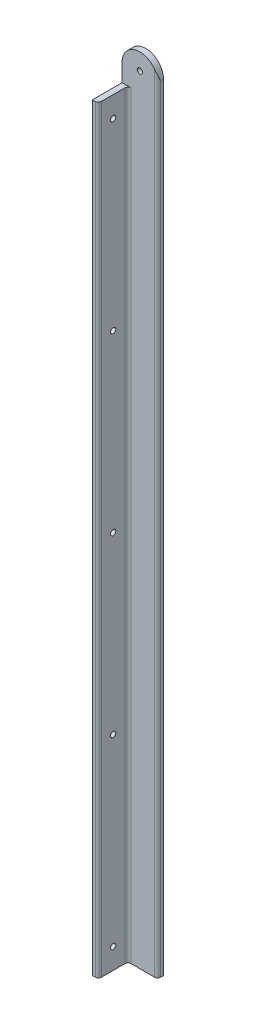
SolidWorks part; units mm, degrees
material "6061 Alloy"
ref_plane "Front Plane" through (0, 0, 0) normal (0, 0, 1) x (1, 0, 0)
ref_plane "Top Plane" through (0, 0, 0) normal (0, 1, 0) x (1, 0, 0)
ref_plane "Right Plane" through (0, 0, 0) normal (1, 0, 0) x (0, 0, -1)
sketch "Sketch2" plane through (0, 0, 0) normal (0, 1, 0) x (1, 0, 0)
  line L0 (0, 0) -> (19.05, 0)
  line L1 (0, 0) -> (0, 19.05)
  line L2 (4.7625, 3.175) -> (17.4625, 3.175)
  line L3 (3.175, 4.7625) -> (3.175, 17.4625)
  line L4 (0, 19.05) -> (1.5875, 19.05)
  line L5 (19.05, 1.5875) -> (19.05, 0)
  line L6 (3.175, 3.175) -> (3.175, 19.05) construction
  line L7 (3.175, 3.175) -> (19.05, 3.175) construction
  arc A0 (3.175, 17.4625) -> (1.5875, 19.05) centre (1.5875, 17.4625) ccw
  arc A1 (3.175, 4.7625) -> (4.7625, 3.175) centre (4.7625, 4.7625) ccw
  arc A2 (17.4625, 3.175) -> (19.05, 1.5875) centre (17.4625, 1.5875) cw
  dimension "D2" = 1.5875
  dimension "D1" = 3.175
extrude "Boss-Extrude1" add sketch "Sketch2" along normal blind 431.8
sketch "Sketch4" plane through (3.175, 0, 0) normal (1, 0, 0) x (0, 0, -1)
  line L0 (19.05, 431.8) -> (19.05, 406.4)
  line L1 (19.05, 431.8) -> (19.05, 0) construction
  line L2 (19.05, 406.4) -> (3.175, 406.4)
  line L3 (3.175, 431.8) -> (3.175, 0) construction
  line L4 (3.175, 406.4) -> (3.175, 431.8)
  line L5 (3.175, 431.8) -> (19.05, 431.8)
extrude "Cut-Extrude1" cut sketch "Sketch4" against normal blind 6.35
sketch "Sketch5" plane through (3.175, 0, 0) normal (-1, 0, 0) x (0, 0, 1)
  line L8 (-4.7625, 406.4) -> (-3.175, 406.4)
  line L9 (-3.175, 406.4) -> (-3.175, 431.8)
  line L10 (-3.175, 431.8) -> (-4.7625, 431.8)
  line L11 (-4.7625, 431.8) -> (-4.7625, 406.4)
  line L12 (-4.7625, 406.4) -> (-3.175, 406.4)
  line L13 (-3.175, 406.4) -> (-3.175, 431.8)
  line L14 (-3.175, 431.8) -> (-4.7625, 431.8)
  line L15 (-4.7625, 431.8) -> (-4.7625, 406.4)
  dimension "D1" = 0
extrude "Cut-Extrude2" cut sketch "Sketch5" against normal blind 6.35
sketch "Sketch6" plane through (3.175, 0, 0) normal (1, 0, 0) x (0, 0, -1)
  line L0 (19.05, 0) -> (3.175, 0) construction
  line L1 (11.1125, 0) -> (11.1125, 15.875) construction
  line L2 (19.05, 406.4) -> (3.175, 406.4) construction
  line L3 (11.1125, 406.4) -> (11.1125, 390.525) construction
  line L4 (11.1125, 15.875) -> (11.1125, 203.2) construction
  line L5 (11.1125, 203.2) -> (11.1125, 390.525) construction
  circle A1 centre (11.1125, 109.5375) radius 1.4224
  circle A2 centre (11.1125, 203.2) radius 1.4224
  circle A3 centre (11.1125, 296.8625) radius 1.4224
  circle A5 centre (11.1125, 11.1125) radius 1.4224
  circle A6 centre (11.1125, 395.2875) radius 1.4224
  point P12 (11.1125, 203.2)
  point P13 (11.1125, 296.8625)
  point P15 (11.1125, 109.5375)
  dimension "D2" = 2.8448
  dimension "D3" = 2.8448
  dimension "D4" = 2.8448
  dimension "D6" = 2.8448
  dimension "D7" = 2.8448
extrude "Cut-Extrude3" cut sketch "Sketch6" against normal blind 5.08
sketch "Sketch7" plane through (0, 431.8, 0) normal (0, 1, 0) x (1, 0, 0)
  line L8 (17.4625, 3.175) -> (0, 3.175)
  line L9 (0, 3.175) -> (0, 0)
  line L10 (0, 0) -> (19.05, 0)
  line L11 (19.05, 0) -> (19.05, 1.5875)
  line L12 (17.4625, 3.175) -> (0, 3.175)
  line L13 (0, 3.175) -> (0, 0)
  line L14 (0, 0) -> (19.05, 0)
  line L15 (19.05, 0) -> (19.05, 1.5875)
  arc A2 (19.05, 1.5875) -> (17.4625, 3.175) centre (17.4625, 1.5875) ccw
  arc A3 (19.05, 1.5875) -> (17.4625, 3.175) centre (17.4625, 1.5875) ccw
  dimension "D1" = 0
extrude "Cut-Extrude4" cut sketch "Sketch7" against normal blind 6.35
sketch "Sketch8" plane through (0, 0, -3.175) normal (0, 0, -1) x (-1, 0, 0)
  line L0 (0, 425.45) -> (0, 416.56) construction
  line L1 (0, 425.45) -> (0, 406.4) construction
  line L2 (0, 416.56) -> (-9.525, 416.56) construction
  circle A0 centre (-9.525, 416.56) radius 1.4224
  dimension "D1" = 2.8448
extrude "Cut-Extrude5" cut sketch "Sketch8" against normal blind 5.08
ref_plane "Plane1" through (0, 0, 2.54) normal (0, 0, 1) x (1, 0, 0)
mirror "Mirror3" about plane through (0, 0, 2.54) normal (0, 0, 1) of bodies 106
sketch "Sketch9" plane through (0, 0, 2.54) normal (0, 0, 1) x (1, 0, 0)
  line L1 (-6.6248, 469.5409) -> (22.2362, 469.5409)
  line L2 (-6.6248, 469.5409) -> (-6.6248, -77.9837)
  line L3 (-6.6248, -77.9837) -> (22.2362, -77.9837)
  line L4 (22.2362, 469.5409) -> (22.2362, -77.9837)
extrude "Cut-Extrude6" cut sketch "Sketch9" against normal blind 30.48
sketch "Sketch10" plane through (0, 0, 8.255) normal (0, 0, 1) x (1, 0, 0)
  line L0 (9.525, 416.56) -> (9.525, 415.925) construction
  line L1 (2.8867, 422.7557) -> (0, 425.45) construction
  line L3 (19.05, 415.925) -> (19.05, 425.45)
  line L4 (19.05, 425.45) -> (0, 425.45)
  line L5 (0, 415.925) -> (0, 425.45)
  line L7 (19.05, 425.45) -> (16.1633, 422.7557) construction
  arc A1 (19.05, 415.925) -> (0, 415.925) centre (9.525, 415.925) ccw
  line M4 (17.4625, 425.45) -> (0, 425.45)
  line M5 (0, 425.45) -> (0, 406.4)
  line M9 (17.4625, 0) -> (17.4625, 425.45)
extrude "Cut-Extrude7" cut sketch "Sketch10" against normal blind 5.08 contours A1 L3 L4 M9 | A1 M9 M4 | A1 L4 M5 region at (18.3487, 422.3469, 8.255) region at (2.1276, 423.3224, 8.255) region at (15.5776, 424.2422, 8.255)
